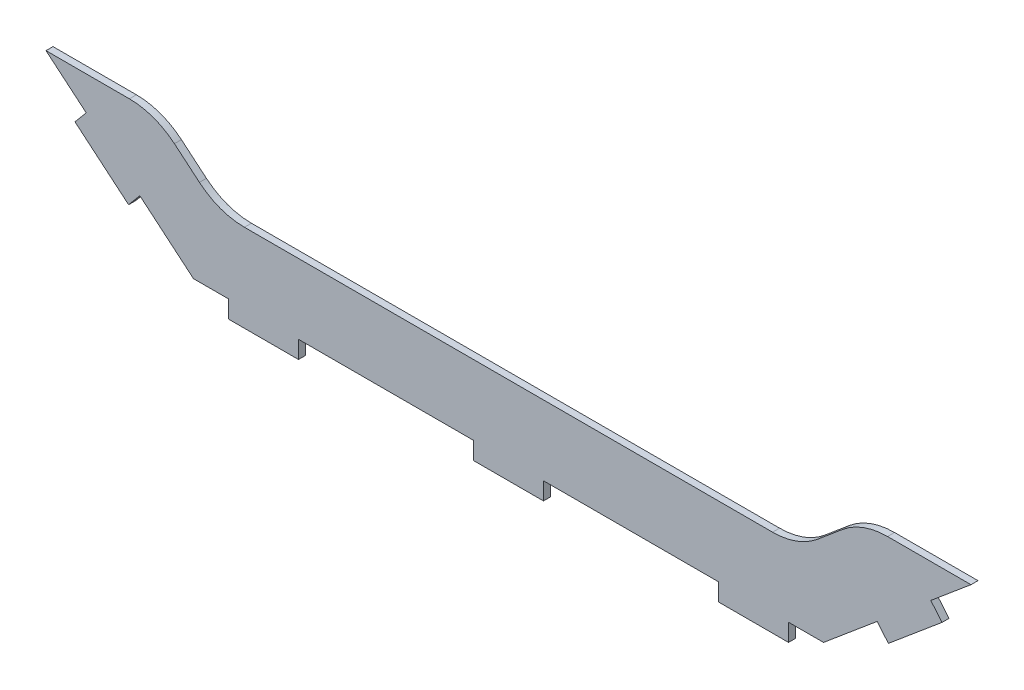
SolidWorks part; units mm, degrees
material "PBT General Purpose"
ref_plane "Front Plane" through (0, 0, 0) normal (0, 0, 1) x (1, 0, 0)
ref_plane "Top Plane" through (0, 0, 0) normal (0, 1, 0) x (1, 0, 0)
ref_plane "Right Plane" through (0, 0, 0) normal (1, 0, 0) x (0, 0, -1)
sketch "frame_outline" plane through (0, 0, 0) normal (0, 0, 1) x (1, 0, 0)
  line L89 (0.5, 0) -> (3, 0)
  line L99 (3, 0) -> (3, -0.25)
  line L100 (3, -0.25) -> (4, -0.25)
  line L101 (4, -0.25) -> (4, 0)
  line L102 (4, 0) -> (4.5, 0)
  line L103 (4.5, 0) -> (5.266, 0.6428)
  line L104 (5.266, 0.6428) -> (5.4267, 0.4513)
  line L105 (5.4267, 0.4513) -> (6.1928, 1.0941)
  line L106 (6.1928, 1.0941) -> (6.0321, 1.2856)
  line L107 (6.0321, 1.2856) -> (6.6066, 1.7677)
  line L108 (6.6066, 1.7677) -> (5.0509, 1.7677)
  line L109 (5.0509, 1.7677) -> (4.136, 1)
  line L110 (4.136, 1) -> (-4.136, 1)
  line L111 (-0.5, 0) -> (-3, 0)
  line L112 (-3, 0) -> (-3, -0.25)
  line L113 (-3, -0.25) -> (-4, -0.25)
  line L114 (-4, -0.25) -> (-4, 0)
  line L115 (-4, 0) -> (-4.5, 0)
  line L116 (-4.5, 0) -> (-5.266, 0.6428)
  line L117 (-5.266, 0.6428) -> (-5.4267, 0.4513)
  line L118 (-5.4267, 0.4513) -> (-6.1928, 1.0941)
  line L119 (-6.1928, 1.0941) -> (-6.0321, 1.2856)
  line L120 (-6.0321, 1.2856) -> (-6.6066, 1.7677)
  line L121 (-6.6066, 1.7677) -> (-5.0509, 1.7677)
  line L122 (-5.0509, 1.7677) -> (-4.136, 1)
  line L123 (-0.5, 0) -> (-0.5, -0.25)
  line L124 (-0.5, -0.25) -> (0.5, -0.25)
  line L125 (0.5, -0.25) -> (0.5, 0)
  point P0 (0, -0.25)
  dimension "D2" = 1
  dimension "D3" = 0.5
  dimension "D4" = 1
  dimension "D5" = 0.25
  dimension "D6" = 0.25
  dimension "D7" = 0.25
  dimension "D8" = 140
  dimension "D9" = 1
  dimension "D10" = 140
  dimension "D11" = 1
  dimension "D12" = 0.75
  dimension "D13" = 1
  dimension "D14" = 1
  dimension "D15" = 3
  dimension "D16" = 1
  dimension "D17" = 0.25
  dimension "D18" = 3
extrude "Boss-Extrude1" add sketch "frame_outline" along normal mid plane 0.1 contours L89 L99 L100 L101 L102 L103 L104 L105 L106 L107 L108 L109 L110 L122 L121 L120 L119 L118 L117 L116 L115 L114 L113 L112 L111 L123 L124 L125
fillet "Fillet1" radius 1 4 edges at (4.136, 1, 0) (5.0509, 1.7677, 0) (-4.136, 1, 0) (-5.0509, 1.7677, 0)
equation "\"t\"= 0.25'thickness of the sheets"
equation "\"t_cf\" = 0.115'thickness of single carbon fiber layer"
equation "\"t_kapton\" = 0.025'thickness of single Kapton flex layer"
equation "\"t_fr4\" = 0.1'thickness of FR4 with copper layer"
equation "\"joint_flex\"= 0.1'Width of flextures gap"
equation "\"joint_flex_eff\"= 0.02'Width of flecture after castelation"
equation "\"joint_fold\"= 0.2'Width of folding joints for 90deg fold"
equation "\"gap_tolerance\"= 0.002'Width to have interfecence fit between carbon fiber inserts"
equation "\"assemble_angle\"= 90'Angle of assembly parts"
equation "\"D1@Boss-Extrude1\"=0.1"
equation "\"link_lift\"= 0.5'Actuation linkage amplification for the lift motion"
equation "\"link_swing\"= 0.45'Actuation linkage amplification for the swing motion"
